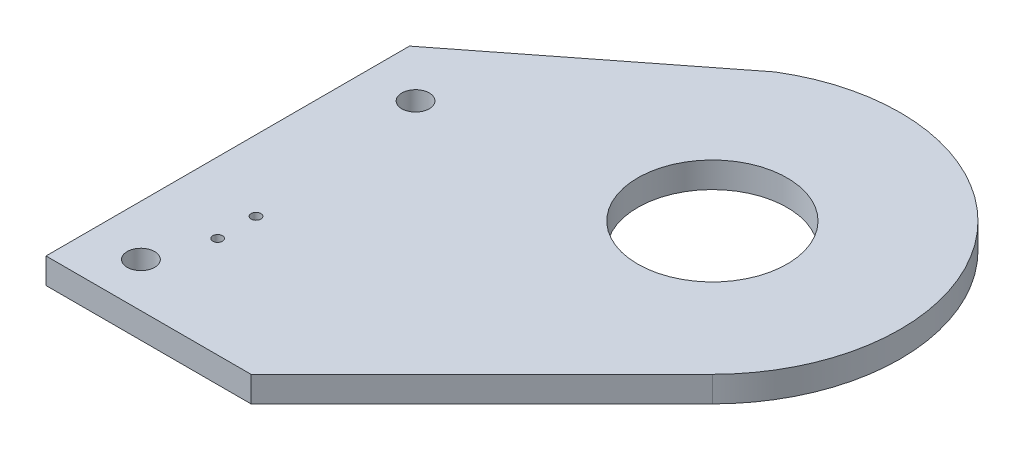
SolidWorks part; units mm, degrees
ref_plane "Front Plane" through (0, 0, 0) normal (0, 0, 1) x (1, 0, 0)
ref_plane "Top Plane" through (0, 0, 0) normal (0, 1, 0) x (1, 0, 0)
ref_plane "Right Plane" through (0, 0, 0) normal (1, 0, 0) x (0, 0, -1)
sketch "Sketch2" plane through (0, 0, 0) normal (0, 1, 0) x (1, 0, 0)
  line L0 (50.7609, 129.6827) -> (50.7609, 0) construction
  line L1 (0, 0) -> (50.7609, 0)
  line L2 (0, 0) -> (0, 90)
  line L3 (0, 129.6827) -> (50.7609, 129.6827) construction
  line L6 (107.8805, 57.1195) -> (50.7609, 0)
  line L8 (0, 129.6827) -> (0, 90) construction
  line L9 (0, 90) -> (75, 90) construction
  line L10 (0, 90) -> (50.7609, 129.6827)
  arc A1 (50.7609, 129.6827) -> (107.8805, 57.1195) centre (75, 90) cw
  dimension "D1" = 90
  dimension "D3" = 46.5
  dimension "D2" = 75
  dimension "D5" = 45
base flange "Base-Flange1" sketch "Sketch2" thickness 6.35 reverse thickness direction no parameters "D1"=0.7366
sketch "Sketch8" plane through (0, 0, 0) normal (0, 1, 0) x (1, 0, 0)
  line L1 (0, 90) -> (0, 0) construction
  line L2 (0, 45) -> (79.3207, 45) construction
  line L3 (0, 90) -> (121.5, 90) construction
  line L4 (79.3207, 28.5598) -> (79.3207, 90) construction
  line L5 (50.7609, 0) -> (107.8805, 57.1195) construction
  line L6 (0, 90) -> (0, 0) construction
  circle A1 centre (12.5, 79) radius 3.4
  circle A3 centre (12.5, 11) radius 3.4
  arc A4 (107.8805, 57.1195) -> (50.7609, 129.6827) centre (75, 90) ccw construction
  dimension "D1" = 6.8
  dimension "D3" = 12.5
  dimension "D2" = 11
extrude "Cut-Extrude1" cut sketch "Sketch8" against normal through all normal cut yes
sketch "Sketch9" plane through (0, 0, 0) normal (0, 1, 0) x (1, 0, 0)
  arc A0 (107.8805, 57.1195) -> (50.7609, 129.6827) centre (75, 90) ccw construction
  arc A1 (107.8805, 57.1195) -> (50.7609, 129.6827) centre (75, 90) ccw construction
  circle A2 centre (75, 90) radius 18.5
  dimension "D1" = 37
extrude "Cut-Extrude2" cut sketch "Sketch9" against normal through all normal cut yes
sketch "Sketch10" plane through (0, 0, 0) normal (0, 1, 0) x (1, 0, 0)
  circle A0 centre (75, 111.25) radius 1.5
  circle A1 centre (75, 68.75) radius 1.5
  circle A2 centre (75, 90) radius 18.5 construction
  circle A3 centre (75, 90) radius 18.5 construction
  circle A4 centre (75, 90) radius 21.25 construction
  dimension "D1" = 3
  dimension "D2" = 3
  dimension "D3" = 42.5
extrude "Cut-Extrude3" [suppressed] cut sketch "Sketch10" against normal through all
sketch "Sketch11" plane through (0, 0, 0) normal (0, 1, 0) x (1, 0, 0)
  line L0 (28.5, 90) -> (28.5, 112.2801) construction
  line L1 (50.7609, 129.6827) -> (0, 90) construction
  line L2 (17.5, 34.5) -> (17.5, 25) construction
  line L3 (28.5, 90) -> (0, 90) construction
  line L4 (0, 0) -> (50.7609, 0) construction
  circle A0 centre (75, 90) radius 18.5 construction
  circle A1 centre (75, 90) radius 18.5 construction
  circle A2 centre (75, 90) radius 46.5 construction
  circle A3 centre (17.5, 25) radius 1.2
  circle A4 centre (17.5, 34.5) radius 1.2
  dimension "D1" = 93
  dimension "D2" = 2.4
  dimension "D3" = 9.5
  dimension "D5" = 25
  dimension "D4" = 11
extrude "Cut-Extrude4" cut sketch "Sketch11" against normal through all normal cut yes
sketch "Bend-Lines1" [suppressed] plane through (0, 0, 0) normal (0, 1, 0) x (1, 0, 0)
sketch "Bounding-Box1" [suppressed] plane through (0, 0, 0) normal (0, 1, 0) x (1, 0, 0)
sheet metal parameters "Sheet-Metal1" thickness 6.35 parameters "D1"=0.7366
flat pattern "Flat-Pattern1" [suppressed]
sketch "Bend-Lines2" plane through (0, 0, 0) normal (0, 1, 0) x (1, 0, 0)
sketch3d "Bounding-Box2" [suppressed]
  line L0 (37.25, -37.25, 0) -> (37.25, 37.25, 0) construction
  line L1 (-22.5, -37.25, 0) -> (-22.5, 37.25, 0) construction
  line L2 (37.25, -37.25, 0) -> (-22.5, -37.25, 0) construction
  line L3 (37.25, 37.25, 0) -> (-22.5, 37.25, 0) construction
sheet metal parameters "Sheet-Metal2" thickness 6.35 parameters "D1"=0.7366
flat pattern "Flat-Pattern1"
sketch "Bend-Lines2" plane through (0, 0, 0) normal (0, 1, 0) x (1, 0, 0)
sketch3d "Bounding-Box2" [suppressed]
  line L0 (-107.7298, -46.3484, 0) -> (0.0689, 64.7304, 0) construction
  line L1 (-42.0452, -110.0934, 0) -> (65.7535, 0.9853, 0) construction
  line L2 (-107.7298, -46.3484, 0) -> (-42.0452, -110.0934, 0) construction
  line L3 (0.0689, 64.7304, 0) -> (65.7535, 0.9853, 0) construction
sheet metal parameters "Sheet-Metal3" thickness 6.35 parameters "D1"=0.7366
flat pattern "Flat-Pattern1"
sketch "Bend-Lines2" plane through (0, 0, 0) normal (0, 1, 0) x (1, 0, 0)
sketch3d "Bounding-Box2" [suppressed]
  line L0 (-120, -45, 0) -> (-4.6195, 70.3805, 0) construction
  line L1 (-49.6195, -115.3805, 0) -> (65.7609, 0, 0) construction
  line L2 (-120, -45, 0) -> (-49.6195, -115.3805, 0) construction
  line L3 (-4.6195, 70.3805, 0) -> (65.7609, 0, 0) construction
sheet metal parameters "Sheet-Metal4" thickness 6.35 parameters "D1"=0.7366
flat pattern "Flat-Pattern1"
sketch "Bend-Lines2" plane through (0, 0, 0) normal (0, 1, 0) x (1, 0, 0)
sketch3d "Bounding-Box2" [suppressed]
  line L0 (-120, -45, 0) -> (-4.6195, 70.3805, 0) construction
  line L1 (-49.6195, -115.3805, 0) -> (65.7609, 0, 0) construction
  line L2 (-120, -45, 0) -> (-49.6195, -115.3805, 0) construction
  line L3 (-4.6195, 70.3805, 0) -> (65.7609, 0, 0) construction
sheet metal parameters "Sheet-Metal5" thickness 6.35 parameters "D1"=0.7366
flat pattern "Flat-Pattern1"
sketch "Bend-Lines2" plane through (0, 0, 0) normal (0, 1, 0) x (1, 0, 0)
sketch3d "Bounding-Box2" [suppressed]
  line L0 (-120, -45, 0) -> (-4.6195, 70.3805, 0) construction
  line L1 (-49.6195, -115.3805, 0) -> (65.7609, 0, 0) construction
  line L2 (-120, -45, 0) -> (-49.6195, -115.3805, 0) construction
  line L3 (-4.6195, 70.3805, 0) -> (65.7609, 0, 0) construction
equation "\"L1L\"=500"
equation "\"L1Thick\"=6.35"
equation "\"Harm-Drive-Outer\"=74.5"
equation "\"L1-Spacing\"=115.65"
equation "\"L-Bracket-HoleToWall\"=12.5"
equation "\"Bracket-Hole-D\"=6.8"
equation "\"D1@Sketch8\"=\"Bracket-Hole-D\""
equation "\"L-Bracket-HoleToSide\"=11"
equation "\"D3@Sketch8\"=\"L-Bracket-HoleToWall\""
equation "\"D2@Sketch8\"=\"L-Bracket-HoleToSide\""
